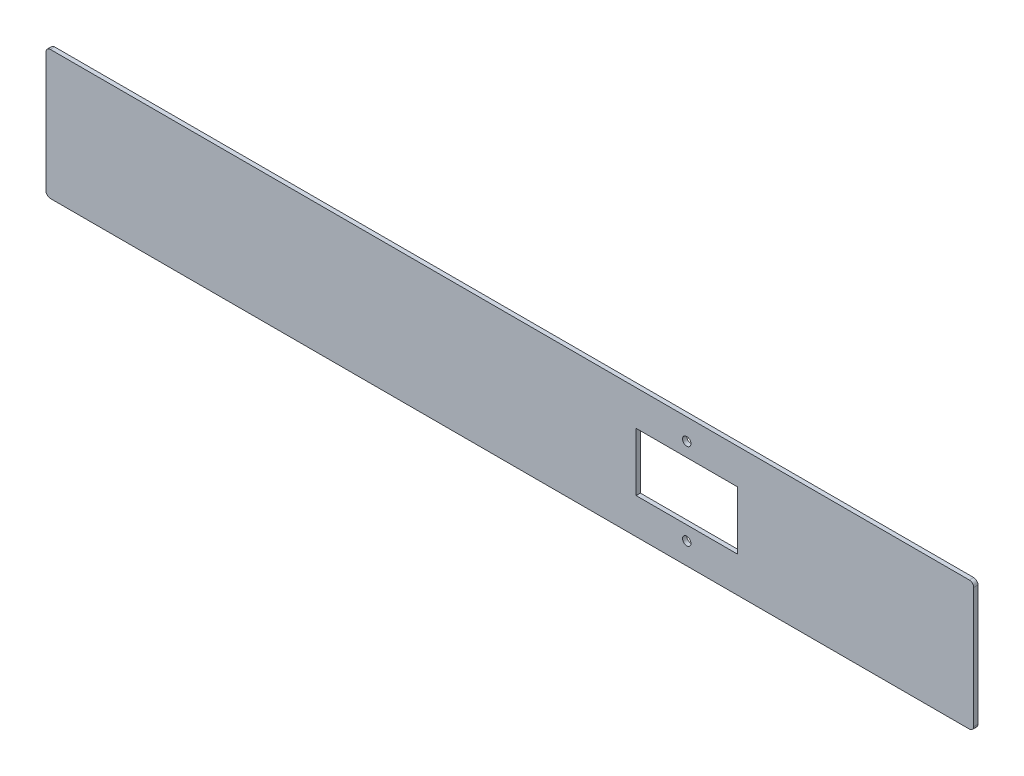
SolidWorks part; units mm, degrees
ref_plane "Front Plane" through (0, 0, 0) normal (0, 0, 1) x (1, 0, 0)
ref_plane "Top Plane" through (0, 0, 0) normal (0, 1, 0) x (1, 0, 0)
ref_plane "Right Plane" through (0, 0, 0) normal (1, 0, 0) x (0, 0, -1)
sketch "Sketch1" plane through (0, 0, 0) normal (0, 0, 1) x (1, 0, 0)
  line L1 (-352.9248, 25.5535) -> (77.0752, 25.5535)
  line L2 (-352.9248, 25.5535) -> (-352.9248, -34.2965)
  line L3 (-352.9248, -34.2965) -> (77.0752, -34.2965)
  line L4 (77.0752, 25.5535) -> (77.0752, -34.2965)
  line L5 (-79.4248, 9.2035) -> (-32.4248, 9.2035)
  line L6 (-79.4248, 9.2035) -> (-79.4248, -17.7965)
  line L7 (-79.4248, -17.7965) -> (-32.4248, -17.7965)
  line L8 (-32.4248, 9.2035) -> (-32.4248, -17.7965)
  circle A0 centre (-55.9248, 15.7035) radius 1.95
  circle A1 centre (-55.9248, -24.2965) radius 1.95
  point P12 (-55.9248, 9.2035)
  dimension "D3" = 133
  dimension "D4" = 40
  dimension "D1" = 430
  dimension "D2" = 59.85
  dimension "D5" = 10
  dimension "D6" = 47
  dimension "D7" = 27
  dimension "D8" = 6.5
extrude "Boss-Extrude1" add sketch "Sketch1" along normal blind 2
fillet "Fillet1" radius 2 4 edges at (77.0752, 25.5535, 1) (77.0752, -34.2965, 1) (-352.9248, -34.2965, 1) (-352.9248, 25.5535, 1)
